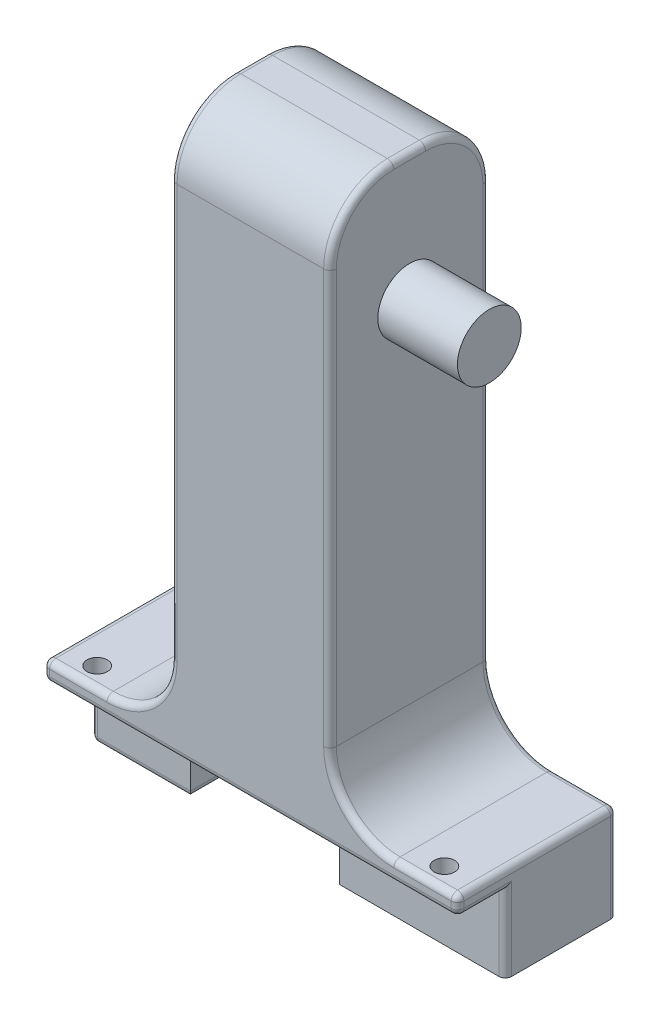
SolidWorks part; units mm, degrees
ref_plane "Front Plane" through (0, 0, 0) normal (0, 0, 1) x (1, 0, 0)
ref_plane "Top Plane" through (0, 0, 0) normal (0, 1, 0) x (1, 0, 0)
ref_plane "Right Plane" through (0, 0, 0) normal (1, 0, 0) x (0, 0, -1)
sketch "Sketch2" plane through (0, 0, 0) normal (0, 1, 0) x (1, 0, 0)
  line L1 (-32.5, -12.5) -> (32.5, -12.5)
  line L2 (-32.5, -12.5) -> (-32.5, 12.5)
  line L3 (-32.5, 12.5) -> (32.5, 12.5)
  line L4 (32.5, -12.5) -> (32.5, 12.5)
  line L5 (-32.5, -12.5) -> (32.5, 12.5) construction
  line L6 (-32.5, 12.5) -> (32.5, -12.5) construction
  point P0 (0, 0)
  dimension "D1" = 65
  dimension "D2" = 25
extrude "Boss-Extrude1" add sketch "Sketch2" along normal blind 3
sketch "Sketch3" plane through (0, 0, 0) normal (0, -1, 0) x (1, 0, 0)
  line L0 (32.5, -12.5) -> (-32.5, -12.5) construction
  line L1 (-32.5, 5) -> (-16.9, 5)
  line L2 (-32.5, 5) -> (-32.5, -12.5)
  line L3 (-32.5, -12.5) -> (-16.9, -12.5)
  line L4 (-16.9, 5) -> (-16.9, -12.5)
  line L10 (32.5, 5) -> (6.5, 5)
  line L12 (6.5, 5) -> (6.5, 0)
  line L13 (6.5, 0) -> (12.5, 0)
  line L14 (12.5, 0) -> (12.5, -12.5)
  line L15 (32.5, -12.5) -> (-32.5, -12.5) construction
  line L16 (12.5, -12.5) -> (32.5, -12.5)
  line L17 (32.5, -12.5) -> (32.5, 5)
  line L18 (-32.5, -12.5) -> (-32.5, 12.5) construction
  point P16 (0, 0)
  dimension "D1" = 15.6
  dimension "D2" = 26
  dimension "D3" = 20
  dimension "D4" = 17.5
extrude "Boss-Extrude2" add sketch "Sketch3" along normal blind 12
sketch "Sketch5" plane through (0, 3, 0) normal (0, 1, 0) x (1, 0, 0)
  circle A0 centre (27.2349, -9.2897) radius 1.6
  circle A1 centre (-27.2349, -9.2897) radius 1.6
  circle A2 centre (27.2349, -9.2897) radius 1.6 construction
extrude "Cut-Extrude1" cut sketch "Sketch5" against normal through all
sketch "Sketch6" plane through (0, 3, 0) normal (0, 1, 0) x (1, 0, 0)
  line L0 (-32.5, -12.5) -> (32.5, -12.5) construction
  line L1 (12.5, -12.5) -> (-12.5, -12.5)
  line L2 (12.5, -12.5) -> (12.5, 12.5)
  line L3 (12.5, 12.5) -> (-12.5, 12.5)
  line L4 (-12.5, -12.5) -> (-12.5, 12.5)
  line L5 (32.5, 12.5) -> (-32.5, 12.5) construction
  line L6 (0, -20.7065) -> (0, 20.7065) construction
  point P12 (0, 0)
  dimension "D1" = 25
extrude "Boss-Extrude3" add sketch "Sketch6" along normal blind 84.9
sketch "Sketch7" plane through (12.5, 0, 0) normal (1, 0, 0) x (0, 0, -1)
  line L0 (12.5, 87.9) -> (12.5, 3) construction
  line L2 (-12.5, 87.9) -> (-12.5, 3) construction
  line L3 (-12.5, 87.9) -> (12.5, 87.9) construction
  circle A0 centre (0, 67.9) radius 12.5
  point P4 (0, 0)
  dimension "D1" = 20
sketch "Sketch9" plane through (12.5, 0, 0) normal (1, 0, 0) x (0, 0, -1)
  circle A0 centre (0, 67.9) radius 5
  point P3 (0, 0)
  dimension "D1" = 10
extrude "Boss-Extrude4" add sketch "Sketch9" along normal blind 12.5
sketch "Sketch8" plane through (-12.5, 0, 0) normal (-1, 0, 0) x (0, 0, 1)
  line L0 (12.5, 87.9) -> (12.5, 3) construction
  line L1 (-12.5, 87.9) -> (-12.5, 3) construction
  circle A1 centre (0, 67.9) radius 12.5
  point P7 (0, 0)
ref_axis "Axis1" through (-18.9714, 67.9, 0) along (1, 0, 0)
sketch "Sketch10" plane through (-12.5, 0, 0) normal (-1, 0, 0) x (0, 0, 1)
  line L0 (-3.75, 72.2589) -> (-3.75, 78.7589)
  line L1 (3.75, 72.2589) -> (3.75, 78.7589)
  line L2 (-3.75, 63.5411) -> (-3.75, 57.0411)
  line L3 (3.75, 63.5411) -> (3.75, 57.0411)
  line L4 (0, 37.8885) -> (0, 97.9115) construction
  line L5 (-3.75, 78.7589) -> (-2.4534, 85.3804)
  line L6 (3.75, 78.7589) -> (2.4534, 85.3804)
  line L7 (-27.0629, 67.9) -> (27.0629, 67.9) construction
  line L8 (3.75, 57.0411) -> (2.4534, 50.4196)
  line L9 (-3.75, 57.0411) -> (-2.4534, 50.4196)
  arc A0 (-3.75, 72.2589) -> (-3.75, 63.5411) centre (0, 67.9) ccw
  arc A1 (2.4534, 85.3804) -> (-2.4534, 85.3804) centre (0, 84.9) ccw
  arc A2 (2.4534, 50.4196) -> (-2.4534, 50.4196) centre (0, 50.9) cw
  arc A3 (3.75, 63.5411) -> (3.75, 72.2589) centre (0, 67.9) ccw
  point P15 (0, 67.9)
  point P22 (0, 67.9)
  dimension "D1" = 11.5
  dimension "D4" = 5
  dimension "D2" = 7.5
  dimension "D3" = 6.5
  dimension "D5" = 17
extrude "Cut-Extrude2" cut sketch "Sketch10" against normal blind 3
sketch "Sketch11" plane through (-9.5, 0, 0) normal (-1, 0, 0) x (0, 0, 1)
  circle A0 centre (0, 67.9) radius 5.75
  arc A1 (3.75, 63.5411) -> (3.75, 72.2589) centre (0, 67.9) ccw construction
extrude "Cut-Extrude3" cut sketch "Sketch11" against normal blind 1
fillet "Fillet1" radius 10 4 edges at (0, 87.9, 12.5) (0, 87.9, -12.5) (-12.5, 3, 0) (12.5, 3, 0)
fillet "Fillet2" radius 1 33 edges at (27.5, 3, 12.5) (15.4289, 5.9289, 12.5) (12.5, 45.45, 12.5) (12.5, 84.9711, 9.5711) (12.5, 87.9, 0) (12.5, 84.9711, -9.5711) (12.5, 45.45, -12.5) (15.4289, 5.9289, -12.5) (-27.5, 3, 12.5) (-15.4289, 5.9289, 12.5) (-12.5, 45.45, 12.5) (-12.5, 84.9711, 9.5711) (-12.5, 87.9, 0) (-12.5, 84.9711, -9.5711) (-27.5, 3, -12.5) (-15.4289, 5.9289, -12.5) (-24.7, -12, 5) (-16.9, -12, -3.75) (-24.7, -12, -12.5) (-32.5, -12, -3.75) (-32.5, 1.5, 12.5) (-32.5, -6, 5) (-32.5, 0, 8.75) (32.5, 1.5, 12.5) (32.5, -6, 5) (32.5, 0, 8.75) (0, 0, 12.5) (-32.5, -4.5, -12.5) (-32.5, 3, 0) (32.5, 3, 0) (32.5, -4.5, -12.5) (27.5, 3, -12.5) (-12.5, 45.45, -12.5)
